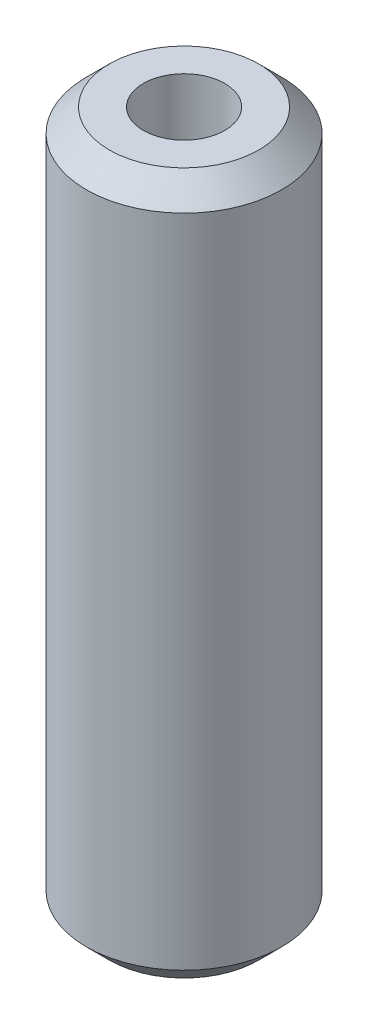
SolidWorks part; units mm, degrees
ref_plane "Front Plane" through (0, 0, 0) normal (0, 0, 1) x (1, 0, 0)
ref_plane "Top Plane" through (0, 0, 0) normal (0, 1, 0) x (1, 0, 0)
ref_plane "Right Plane" through (0, 0, 0) normal (1, 0, 0) x (0, 0, -1)
sketch "Sketch1" plane through (0, 0, 0) normal (0, 1, 0) x (1, 0, 0)
  circle A0 centre (0, 0) radius 20
  dimension "SHAFT_OD" = 40
extrude "Boss-Extrude1" add sketch "Sketch1" along normal blind 143.7519
sketch "Sketch2" plane through (0, 0, 0) normal (0, 1, 0) x (1, 0, 0)
  circle A0 centre (0, 0) radius 8.3462
  dimension "BORE_D" = 16.6925
extrude "Cut-Extrude1" cut sketch "Sketch2" along normal through all
chamfer "Chamfer1" distance 4.7047 angle 45 2 edges at (0, 143.7519, 20) (0, 0, 20)
